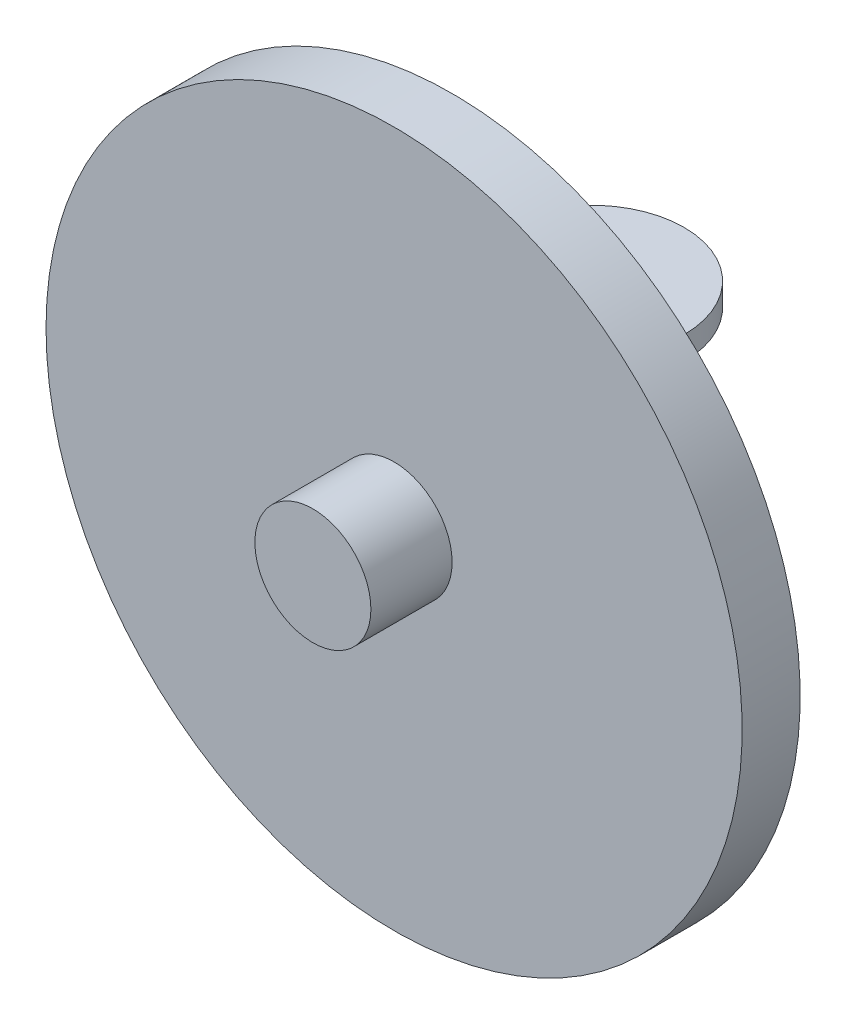
SolidWorks part; units mm, degrees
ref_plane "Front Plane" through (0, 0, 0) normal (0, 0, 1) x (1, 0, 0)
ref_plane "Top Plane" through (0, 0, 0) normal (0, 1, 0) x (1, 0, 0)
ref_plane "Right Plane" through (0, 0, 0) normal (1, 0, 0) x (0, 0, -1)
sketch "Sketch1" plane through (0, 0, 0) normal (0, 0, 1) x (1, 0, 0)
  circle A0 centre (0, 0) radius 25
  dimension "D1" = 50
extrude "Boss-Extrude1" add sketch "Sketch1" along normal blind 35
sketch "Sketch2" plane through (0, 0, 0) normal (0, 0, -1) x (-1, 0, 0)
  circle A0 centre (0, 0) radius 150
  dimension "D1" = 300
extrude "Boss-Extrude2" add sketch "Sketch2" along normal blind 25
sketch "Sketch3" plane through (0, 0, -25) normal (0, 0, -1) x (-1, 0, 0)
  line L1 (-40, 50) -> (40, 50)
  line L2 (-40, 50) -> (-40, -50)
  line L3 (-40, -50) -> (40, -50)
  line L4 (40, 50) -> (40, -50)
  line L5 (-40, 50) -> (40, -50) construction
  line L6 (-40, -50) -> (40, 50) construction
  line L7 (40, 40) -> (-40, 40)
  line L8 (40, 40) -> (40, -40)
  line L9 (40, -40) -> (-40, -40)
  line L10 (-40, 40) -> (-40, -40)
  line L11 (40, 40) -> (-40, -40) construction
  line L12 (40, -40) -> (-40, 40) construction
  point P0 (0, 0)
  point P7 (0, 0)
  dimension "D1" = 80
  dimension "D2" = 100
  dimension "D3" = 80
extrude "Boss-Extrude3" add sketch "Sketch3" along normal blind 100 contours L7 L4 L1 L2 | L4 L9 L2 L3 region at (0, 45, -25) region at (0, -45, -25)
sketch "Sketch5" plane through (0, -50, 0) normal (0, -1, 0) x (1, 0, 0)
  line L0 (0, -125) -> (0, -25) construction
  line L1 (40, -125) -> (-40, -125) construction
  line L2 (-150, -25) -> (150, -25) construction
  circle A0 centre (0, -75) radius 25
  dimension "D1" = 50
extrude "Cut-Extrude1" cut sketch "Sketch5" against normal blind 134
fillet "Fillet1" radius 40 4 edges at (40, 45, -125) (-40, 45, -125) (-40, -45, -125) (40, -45, -125)
